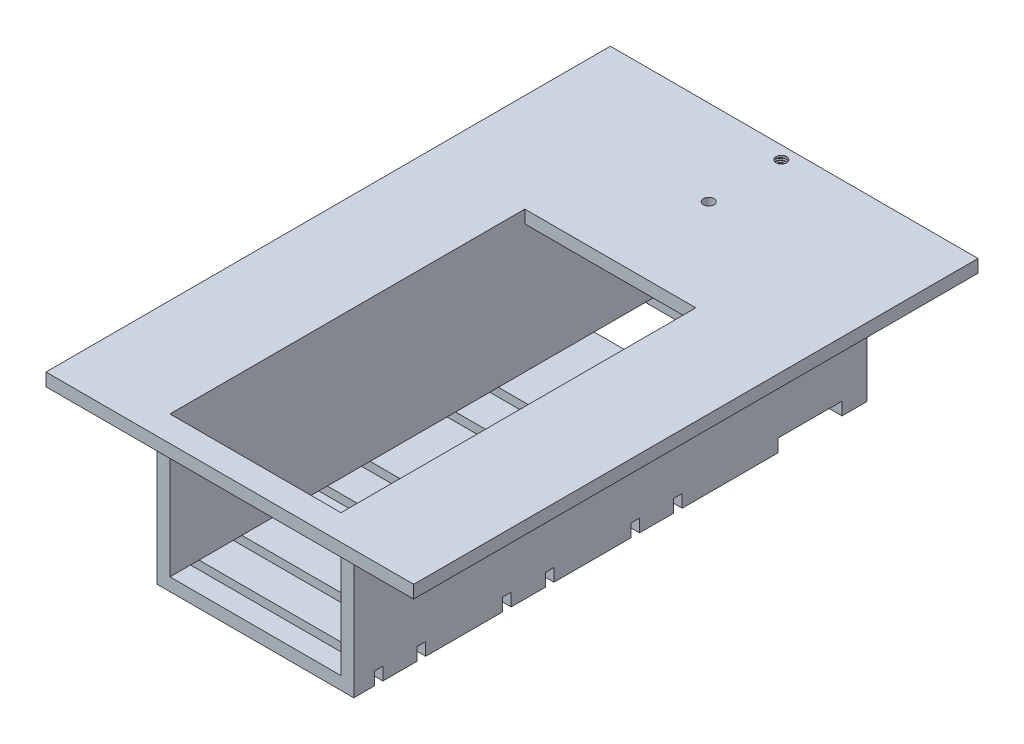
SolidWorks part; units mm, degrees
ref_plane "Front Plane" through (0, 0, 0) normal (0, 0, 1) x (1, 0, 0)
ref_plane "Top Plane" through (0, 0, 0) normal (0, 1, 0) x (1, 0, 0)
ref_plane "Right Plane" through (0, 0, 0) normal (1, 0, 0) x (0, 0, -1)
sketch "Sketch1" plane through (0, 0, 0) normal (0, 0, 1) x (1, 0, 0)
  line L0 (0, 0) -> (23, 0)
  line L1 (23, 0) -> (23, 33)
  line L2 (0, 0) -> (-23, 0)
  line L3 (-23, 0) -> (-23, 33)
  line L6 (-20, 3) -> (20, 3)
  line L9 (23, 33) -> (43, 33)
  line L10 (43, 33) -> (43, 36)
  line L11 (43, 36) -> (20, 36)
  line L12 (20, 36) -> (20, 3)
  line L13 (-23, 33) -> (-43, 33)
  line L14 (-43, 33) -> (-43, 36)
  line L15 (-43, 36) -> (-20, 36)
  line L16 (-20, 36) -> (-20, 3)
  dimension "D1" = 23
  dimension "D2" = 23
  dimension "D3" = 33
  dimension "D4" = 33
  dimension "D5" = 3
  dimension "D6" = 3
  dimension "D7" = 3
  dimension "D8" = 3
  dimension "D9" = 20
  dimension "D10" = 20
  dimension "D11" = 3
extrude "Boss-Extrude1" add sketch "Sketch1" along normal blind 120
sketch "Sketch2" plane through (0, 0, 0) normal (0, 0, 1) x (1, 0, 0)
  line L1 (-20, 36) -> (20, 36)
  line L2 (-20, 36) -> (-20, 3)
  line L3 (-20, 3) -> (20, 3)
  line L4 (20, 36) -> (20, 3)
extrude "Boss-Extrude2" add sketch "Sketch2" along normal blind 1
ref_plane "Plane5" through (0, 36, 0) normal (0, 1, 0) x (1, 0, 0)
sketch "Sketch24" plane through (0, 36, 0) normal (0, 1, 0) x (1, 0, 0)
  line L0 (-43, 0) -> (-43, 6)
  line L1 (-43, 6) -> (43, 6)
  line L2 (43, 6) -> (43, 0)
  line L3 (43, 0) -> (-43, 0) construction
  line L4 (-43, 0) -> (43, 0)
  line L12 (43, 0) -> (-43, 0)
  line L13 (-43, 0) -> (-43, -120)
  line L14 (-43, -120) -> (-20, -120)
  line L15 (-20, -120) -> (-20, -1)
  line L16 (-20, -1) -> (20, -1)
  line L17 (20, -1) -> (20, -120)
  line L18 (20, -120) -> (43, -120)
  line L19 (43, -120) -> (43, 0)
  line L21 (-43, 0) -> (-43, -120)
  line L22 (-43, -120) -> (-20, -120)
  line L23 (-20, -120) -> (-20, -1)
  line L24 (-20, -1) -> (20, -1)
  line L25 (20, -1) -> (20, -120)
  line L26 (20, -120) -> (43, -120)
  line L27 (43, -120) -> (43, 0)
  circle A0 centre (0, 3) radius 1.25
  dimension "D2" = 6
  dimension "D1" = 0
extrude "Boss-Extrude5" add sketch "Sketch24" against normal blind 3 contours L0 L4 L2 L1 region at (-42.1379, 36, -3)
thread "Thread2" pitch 0.5 method cut profile "螺纹线轮廓4" start angle 0, offset 0, length 0, pitch 0.5, diameter 2.5
ref_plane "Plane6" through (-1.25, 36, -3) normal (0, 0, 1) x (-1, 0, 0)
sketch "螺纹线轮廓4" plane through (-1.25, 36, -3) normal (0, 0, 1) x (-1, 0, 0)
  line L0 (0, 0) -> (0, 0.5) construction
  line L1 (0, 0) -> (0.2706, 0.1562)
  line L2 (0.2706, 0.1562) -> (0.2706, 0.2187)
  line L3 (0.2706, 0.2187) -> (0, 0.375)
  line L4 (0.2706, 0.1875) -> (0, 0.1875) construction
  line L11 (0, 0) -> (0, 0.375)
  point P2 (0, 0)
  dimension "Pitch" = 0.5
  dimension "Profile_Angle" = 60
  dimension "Profile_Land" = 0.0625
  dimension "Profile_Height" = 0.2706
sketch "Sketch27" plane through (0, 36, 0) normal (0, 1, 0) x (1, 0, 0)
  line L1 (-43, -120) -> (43, -120)
  line L2 (-43, -120) -> (-43, -126)
  line L3 (-43, -126) -> (43, -126)
  line L4 (43, -120) -> (43, -126)
  dimension "D1" = 6
  dimension "D2" = 86
extrude "Boss-Extrude6" add sketch "Sketch27" against normal blind 3
sketch "Sketch28" plane through (0, 36, 0) normal (0, 1, 0) x (1, 0, 0)
  line L0 (20, -120) -> (20, -1) construction
  line L1 (-20, -1) -> (20, -1)
  line L2 (-20, -1) -> (-20, -37)
  line L3 (-20, -37) -> (20, -37)
  line L4 (20, -1) -> (20, -37)
  line L5 (-43, 6) -> (43, 6) construction
  circle A0 centre (0, -14) radius 1.25
  dimension "D2" = 20
  dimension "D1" = 36
extrude "Boss-Extrude7" add sketch "Sketch28" against normal blind 3
ref_plane "Plane7" through (0, 0, 0) normal (0, -1, 0) x (-1, 0, 0)
sketch "Sketch29" plane through (0, 0, 0) normal (0, -1, 0) x (-1, 0, 0)
  line L0 (-23, -120) -> (-23, 0) construction
  line L1 (-23, -5.7981) -> (23, -5.7981)
  line L2 (-23, -5.7981) -> (-23, -20.7981)
  line L3 (-23, -20.7981) -> (23, -20.7981)
  line L4 (23, -5.7981) -> (23, -20.7981)
  line L5 (23, -120) -> (23, 0) construction
  line L6 (-23, -120) -> (-23, 0) construction
  line L7 (-23, -43.1933) -> (23, -43.1933)
  line L8 (-23, -43.1933) -> (-23, -45.1933)
  line L9 (-23, -45.1933) -> (23, -45.1933)
  line L10 (23, -43.1933) -> (23, -45.1933)
  line L11 (-23, -53.1933) -> (-23, -55.1933)
  line L12 (-23, -53.1933) -> (23, -53.1933)
  line L13 (23, -53.1933) -> (23, -55.1933)
  line L14 (-23, -55.1933) -> (23, -55.1933)
  line L19 (-23, -73.1933) -> (-23, -75.1933)
  line L20 (-23, -73.1933) -> (23, -73.1933)
  line L21 (23, -73.1933) -> (23, -75.1933)
  line L22 (-23, -75.1933) -> (23, -75.1933)
  line L23 (-23, -83.1933) -> (-23, -85.1933)
  line L24 (-23, -83.1933) -> (23, -83.1933)
  line L25 (23, -83.1933) -> (23, -85.1933)
  line L26 (-23, -85.1933) -> (23, -85.1933)
  line L31 (-23, -103.1933) -> (-23, -105.1933)
  line L32 (-23, -103.1933) -> (23, -103.1933)
  line L33 (23, -103.1933) -> (23, -105.1933)
  line L34 (-23, -105.1933) -> (23, -105.1933)
  line L35 (-23, -113.1933) -> (-23, -115.1933)
  line L36 (-23, -113.1933) -> (23, -113.1933)
  line L37 (23, -113.1933) -> (23, -115.1933)
  line L38 (-23, -115.1933) -> (23, -115.1933)
  line L39 (-23, -63.1933) -> (-23, -65.1933) [skipped]
  line L40 (-23, -65.1933) -> (23, -65.1933) [skipped]
  line L41 (23, -63.1933) -> (23, -65.1933) [skipped]
  line L42 (-23, -63.1933) -> (23, -63.1933) [skipped]
  line L43 (-23, -93.1933) -> (-23, -95.1933) [skipped]
  line L44 (-23, -95.1933) -> (23, -95.1933) [skipped]
  line L45 (23, -93.1933) -> (23, -95.1933) [skipped]
  line L46 (-23, -93.1933) -> (23, -93.1933) [skipped]
  dimension "D1" = 2
  dimension "D2" = 8
  dimension "D5" = 15
extrude "Cut-Extrude1" cut sketch "Sketch29" against normal blind 3
